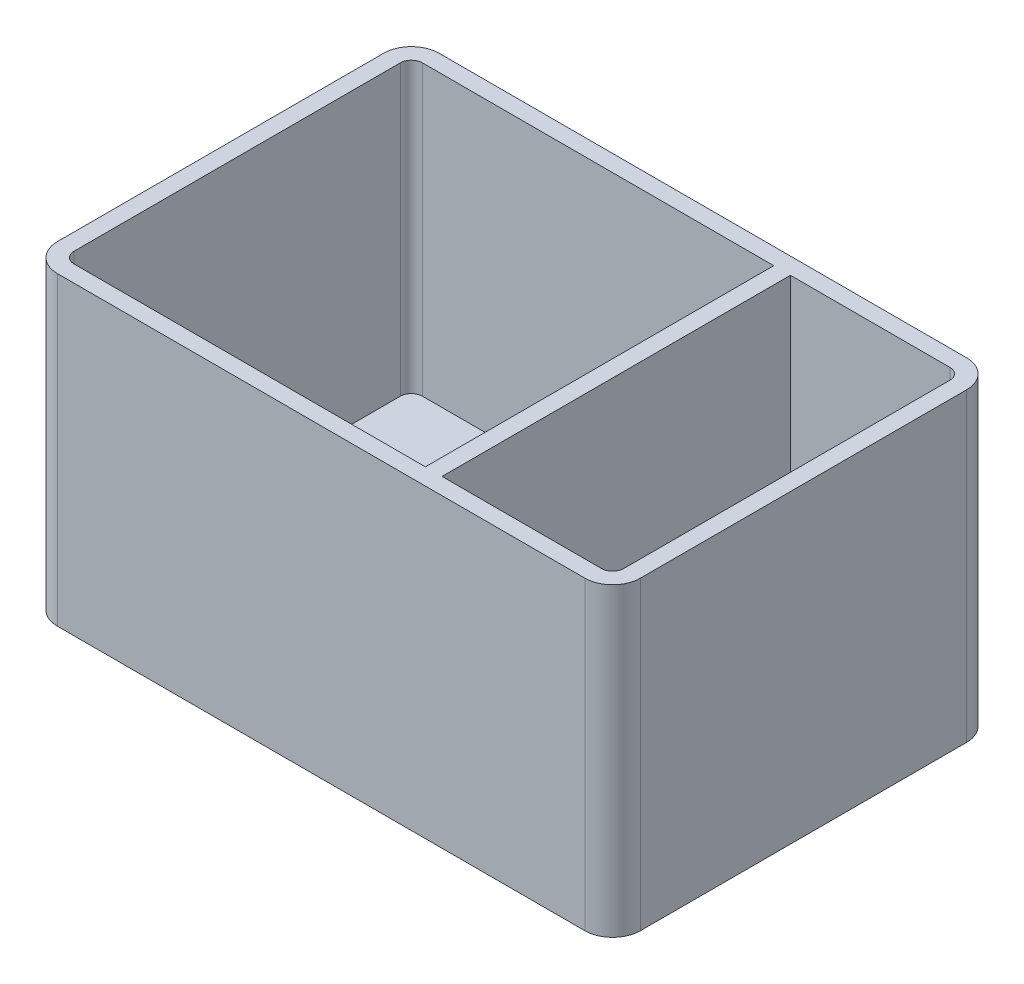
SolidWorks part; units mm, degrees
ref_plane "Front Plane" through (0, 0, 0) normal (0, 0, 1) x (1, 0, 0)
ref_plane "Top Plane" through (0, 0, 0) normal (0, 1, 0) x (1, 0, 0)
ref_plane "Right Plane" through (0, 0, 0) normal (1, 0, 0) x (0, 0, -1)
sketch "Sketch2" plane through (0, 0, 0) normal (0, 1, 0) x (1, 0, 0)
  line L1 (47.5, -34.375) -> (-47.5, -34.375)
  line L2 (52.5, -29.375) -> (52.5, 29.375)
  line L3 (47.5, 34.375) -> (-47.5, 34.375)
  line L4 (-52.5, -29.375) -> (-52.5, 29.375)
  arc A0 (-47.5, -34.375) -> (-52.5, -29.375) centre (-47.5, -29.375) cw
  arc A1 (47.5, -34.375) -> (52.5, -29.375) centre (47.5, -29.375) ccw
  arc A2 (52.5, 29.375) -> (47.5, 34.375) centre (47.5, 29.375) ccw
  arc A3 (-47.5, 34.375) -> (-52.5, 29.375) centre (-47.5, 29.375) ccw
  point P0 (0, 0)
  point P8 (-52.5, -34.375)
  point P13 (52.5, 34.375)
  point P16 (-52.5, 34.375)
  dimension "D3" = 5
  dimension "D1" = 105
  dimension "D2" = 68.75
extrude "Boss-Extrude1" add sketch "Sketch2" along normal blind 55
shell "Shell1" thickness 3 removed face at (0, 55, 0)
sketch "battery_connector_sketch" plane through (0, 3, 0) normal (0, 1, 0) x (1, 0, 0)
  line L0 (-43.2554, -24.8314) -> (-43.2554, -6.8814) construction
  line L1 (-48.2554, -4.8314) -> (-48.2554, -29.1314)
  line L2 (-46.2554, -31.1314) -> (-40.2554, -31.1314)
  line L3 (-40.2554, -2.8314) -> (-46.2554, -2.8314)
  line L4 (-39.5054, -13.4014) -> (-39.5054, -20.5614)
  line L5 (-38.2554, -4.8314) -> (-38.2554, -12.0614)
  line L6 (-38.2554, -29.1314) -> (-38.2554, -21.9014)
  line L7 (-38.2554, -12.0614) -> (-39.5054, -13.4014)
  line L8 (-38.2554, -21.9014) -> (-39.5054, -20.5614)
  line L9 (-41.26, -14.3503) -> (-45.2391, -14.3349)
  arc A0 (-38.2554, -4.8314) -> (-40.2554, -2.8314) centre (-40.2554, -4.8314) ccw
  arc A1 (-48.2554, -29.1314) -> (-46.2554, -31.1314) centre (-46.2554, -29.1314) ccw
  arc A2 (-40.2554, -31.1314) -> (-38.2554, -29.1314) centre (-40.2554, -29.1314) ccw
  arc A3 (-48.2554, -4.8314) -> (-46.2554, -2.8314) centre (-46.2554, -4.8314) cw
  circle A4 centre (-43.2554, -24.8314) radius 2.5
  circle A5 centre (-43.2554, -6.8814) radius 2.5
  arc A6 (-45.2391, -14.3349) -> (-41.26, -14.3503) centre (-43.2554, -15.8564) ccw
  circle A7 centre (-43.2554, -6.8814) radius 2.15
  circle A8 centre (-43.2554, -24.8314) radius 2.15
  dimension "D1" = 4.3
  dimension "D2" = 4.3
extrude "Cut-Extrude1" cut sketch "battery_connector_sketch" against normal blind 2 contours L1 A1 L2 A2 L6 L8 L4 L7 L5 A0 L3 A3
extrude "Cut-Extrude2" cut sketch "battery_connector_sketch<3>" against normal blind 3 contours A7
sketch "battery_connector_sketch<3>" plane through (0, 3, 0) normal (0, 1, 0) x (1, 0, 0) same geometry as "battery_connector_sketch"
extrude "Cut-Extrude3" cut sketch "battery_connector_sketch<4>" against normal blind 3 contours A8
sketch "battery_connector_sketch<4>" plane through (0, 3, 0) normal (0, 1, 0) x (1, 0, 0) same geometry as "battery_connector_sketch"
sketch "Sketch25" plane through (0, 3, 0) normal (0, 1, 0) x (1, 0, 0)
  line L0 (-46.2554, -31.1314) -> (-48.4565, -31.1314)
  line L2 (-46.2554, -2.8314) -> (-49.5, -2.8314)
  line L3 (-49.5, 29.375) -> (-49.5, -29.375) construction
  line L4 (-49.5, -2.8314) -> (-49.5, -29.375)
  line L5 (-48.2554, -29.1314) -> (-48.2554, -4.8314)
  arc A0 (-48.2554, -29.1314) -> (-46.2554, -31.1314) centre (-46.2554, -29.1314) ccw
  arc A1 (-49.5, -29.375) -> (-48.4565, -31.1314) centre (-47.5, -29.375) ccw
  arc A2 (-49.5, -29.375) -> (-47.5, -31.375) centre (-47.5, -29.375) ccw construction
  arc A3 (-48.2554, -4.8314) -> (-46.2554, -2.8314) centre (-46.2554, -4.8314) cw
extrude "Boss-Extrude6" add sketch "Sketch25" along normal blind 12.75
sketch "connector_side_mount_sketch" plane through (-48.2554, 0, 0) normal (1, 0, 0) x (0, 0, -1)
  line L0 (-14.1207, 11.25) -> (-8.6541, 11.25) construction
  line L1 (-4.8314, 1) -> (-29.1314, 1) construction
  line L2 (-2.8314, 15.75) -> (-2.8314, 3) construction
  line L3 (-4.8314, 1) -> (-4.8314, 15.75) construction
  line L5 (-4.8314, 7.2) -> (-29.1314, 7.2)
  line L6 (-4.8314, 7.2) -> (-4.8314, 6)
  line L7 (-4.8314, 6) -> (-29.1314, 6)
  line L8 (-29.1314, 7.2) -> (-29.1314, 6)
  line L9 (-29.1314, 1) -> (-29.1314, 15.75) construction
  circle A0 centre (-9.8914, 11.25) radius 1.55
  circle A1 centre (-24.0714, 11.25) radius 1.505
  line M5 (-4.8314, 1) -> (-4.8314, 15.75)
  line M7 (-29.1314, 15.75) -> (-29.1314, 1)
  dimension "D1" = 3.1
  dimension "D2" = 10.25
  dimension "D4" = 5
  dimension "D3" = 7.06
  dimension "D5" = 1.2
extrude "connector_mount_pins_sockets" cut sketch "connector_side_mount_sketch" against normal blind 2.4 contours A0 | A1
extrude "Boss-Extrude7" add sketch "connector_mount_pins_sockets_sketch<3>" along normal blind 0.7 contours L7 L5 M5 M7 region at (-48.2554, 6.6, 16.9814)
sketch "connector_mount_pins_sockets_sketch<3>" plane through (-48.2554, 0, 0) normal (1, 0, 0) x (0, 0, -1) same geometry as "connector_side_mount_sketch"
sketch "partition-sketch" plane through (0, 3, 0) normal (0, 1, 0) x (1, 0, 0)
  line L0 (47.5, 31.375) -> (-47.5, 31.375) construction
  line L1 (15.7706, 31.375) -> (18.7706, 31.375)
  line L2 (15.7706, 31.375) -> (15.7706, -31.375)
  line L3 (15.7706, -31.375) -> (18.7706, -31.375)
  line L4 (18.7706, 31.375) -> (18.7706, -31.375)
  line L5 (-47.5, -31.375) -> (47.5, -31.375) construction
  line L6 (49.5, -29.375) -> (49.5, 29.375) construction
  dimension "D1" = 3
  dimension "D2" = 30.7294
extrude "partition-boss" add sketch "partition-sketch" along normal blind 52
ref_plane "Plane1" through (18.7706, 0, 0) normal (1, 0, 0) x (0, 0, -1)
sketch "Sketch28" plane through (18.7706, 0, 0) normal (1, 0, 0) x (0, 0, -1)
  line L0 (29.375, 55) -> (29.375, 0) construction
  line L1 (-31.375, 3) -> (31.375, 3) construction
  circle A0 centre (26.075, 6.6) radius 3.5
  dimension "D1" = 7
  dimension "D2" = 3.3
  dimension "D3" = 3.6
extrude "Cut-Extrude4" cut sketch "Sketch28" against normal blind 3 from offset 0 contours A0
